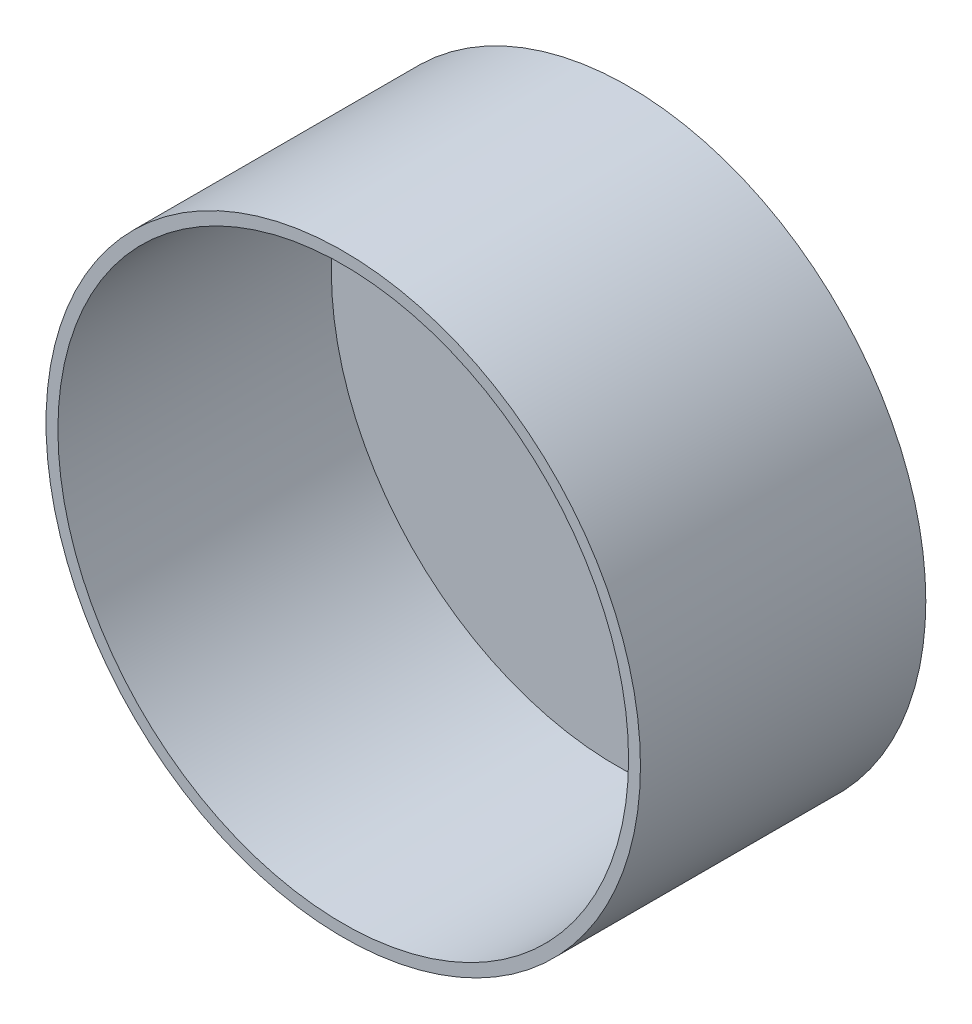
SolidWorks part; units mm, degrees
ref_plane "Front Plane" through (0, 0, 0) normal (0, 0, 1) x (1, 0, 0)
ref_plane "Top Plane" through (0, 0, 0) normal (0, 1, 0) x (1, 0, 0)
ref_plane "Right Plane" through (0, 0, 0) normal (1, 0, 0) x (0, 0, -1)
sketch "Outer Diameter Sketch" plane through (0, 0, 0) normal (0, 0, 1) x (1, 0, 0)
  circle A0 centre (0, 0) radius 125
  dimension "D1" = 250
extrude "Outer Diameter Extrude" add sketch "Outer Diameter Sketch" along normal blind 120
sketch "Inner Diameter Sketch" plane through (0, 0, 120) normal (0, 0, 1) x (1, 0, 0)
  circle A0 centre (0, 0) radius 120
  circle A1 centre (0, 0) radius 125 construction
  dimension "Shell Thickness" = 5
extrude "Inner Diameter Cut" cut sketch "Inner Diameter Sketch" against normal offset from surface (115 mm away) 5 up to face at (125, 0, 0)
